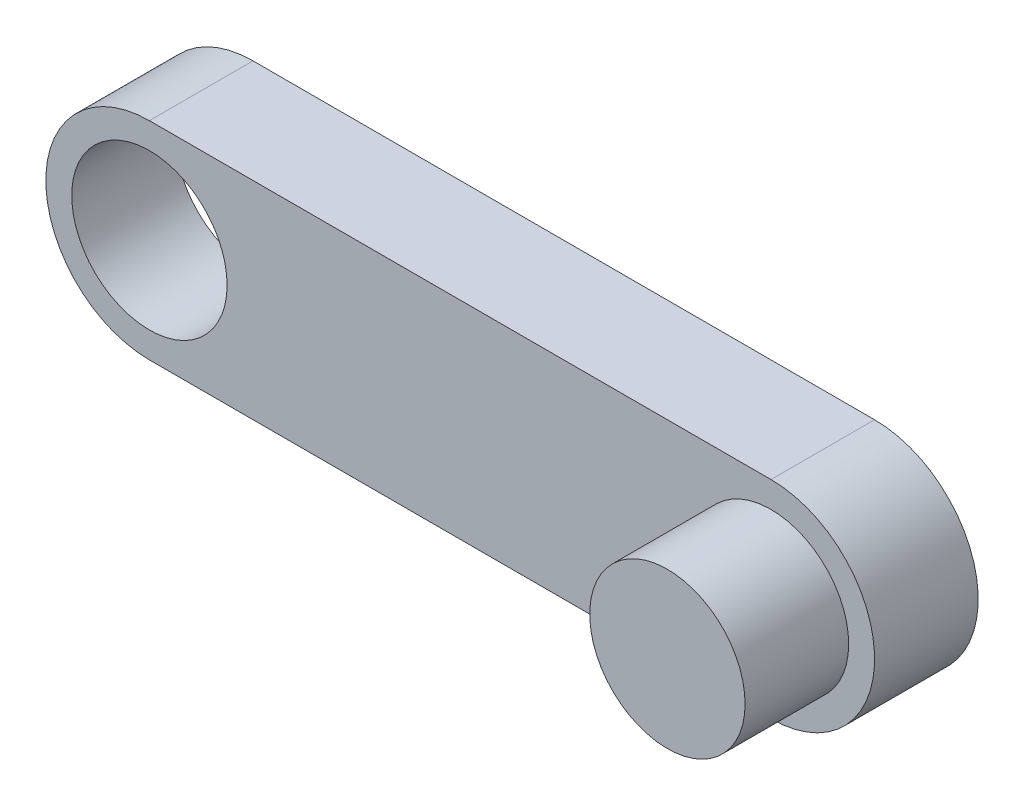
SolidWorks part; units mm, degrees
ref_plane "Front Plane" through (0, 0, 0) normal (0, 0, 1) x (1, 0, 0)
ref_plane "Top Plane" through (0, 0, 0) normal (0, 1, 0) x (1, 0, 0)
ref_plane "Right Plane" through (0, 0, 0) normal (1, 0, 0) x (0, 0, -1)
sketch "Sketch1" plane through (0, 0, 0) normal (0, 0, 1) x (1, 0, 0)
  line L1 (-76.2, -25.4) -> (76.2, -25.4)
  line L2 (-76.2, -25.4) -> (-76.2, 25.4)
  line L3 (-76.2, 25.4) -> (76.2, 25.4)
  line L4 (76.2, -25.4) -> (76.2, 25.4)
  line L5 (-76.2, -25.4) -> (76.2, 25.4) construction
  line L6 (-76.2, 25.4) -> (76.2, -25.4) construction
  circle A0 centre (-76.2, 0) radius 25.4
  circle A1 centre (76.2, 0) radius 25.4
  circle A2 centre (-76.2, 0) radius 19.05
  point P0 (0, 0)
  dimension "D3" = 38.1
  dimension "D1" = 50.8
  dimension "D2" = 152.4
extrude "Boss-Extrude1" add sketch "Sketch1" along normal blind 25.4 contours A0 | L2 L1 L4 L3 | A1
sketch "Sketch2" plane through (0, 0, 25.4) normal (0, 0, 1) x (1, 0, 0)
  circle A0 centre (-76.2, 0) radius 19.05
  arc A1 (-76.2, 25.4) -> (-76.2, -25.4) centre (-76.2, 0) ccw construction
  circle A2 centre (76.2, 0) radius 19.05
  arc A3 (76.2, -25.4) -> (76.2, 25.4) centre (76.2, 0) ccw construction
  dimension "D1" = 38.1
  dimension "D2" = 38.1
extrude "Cut-Extrude1" cut sketch "Sketch2" against normal through all contours A0
sketch "Sketch3" plane through (0, 0, 25.4) normal (0, 0, 1) x (1, 0, 0)
  circle A0 centre (76.2, 0) radius 19.05
  arc A1 (76.2, -25.4) -> (76.2, 25.4) centre (76.2, 0) ccw construction
  dimension "D1" = 38.1
extrude "Boss-Extrude2" add sketch "Sketch3" along normal blind 25.4
